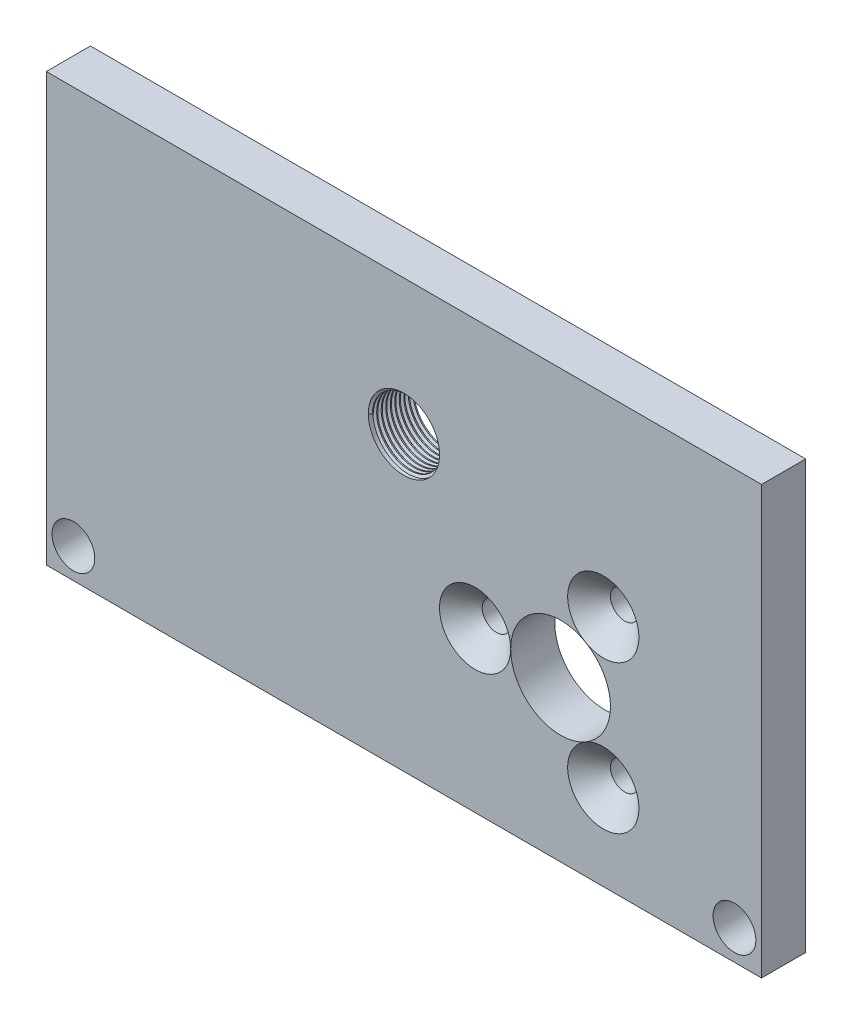
SolidWorks part; units mm, degrees
material "6063-T6"
ref_plane "Plano frontal" through (0, 0, 0) normal (0, 0, 1) x (1, 0, 0)
ref_plane "Plano superior" through (0, 0, 0) normal (0, 1, 0) x (1, 0, 0)
ref_plane "Plano direito" through (0, 0, 0) normal (1, 0, 0) x (0, 0, -1)
sketch "Esboço1" plane through (0, 0, 0) normal (0, 0, 1) x (1, 0, 0)
  line L0 (0, 5.5) -> (0, -19.5) construction
  line L1 (-25.1, 15) -> (25.1, 15)
  line L2 (-25.1, 15) -> (-25.1, -15)
  line L3 (-25.1, -15) -> (25.1, -15)
  line L4 (25.1, 15) -> (25.1, -15)
  line L5 (-25.1, 15) -> (25.1, -15) construction
  line L6 (-25.1, -15) -> (25.1, 15) construction
  line L7 (10.9941, -3.8) -> (10.9941, 4.1456) construction
  line L8 (10.9941, -3.8) -> (13.9941, 1.3962) construction
  circle A0 centre (0, 5.5) radius 2.5
  circle A1 centre (10.9941, -3.8) radius 11 construction
  circle A2 centre (10.9941, -3.8) radius 2.4 construction
  circle A3 centre (0, 5.5) radius 12 construction
  circle A4 centre (0, 5.5) radius 25 construction
  circle A5 centre (10.9941, -3.8) radius 3.5
  circle A6 centre (-23.2, -12.9) radius 1.5
  circle A7 centre (23.2, -12.9) radius 1.5
  circle A8 centre (13.9941, 1.3962) radius 1
  circle A9 centre (13.9941, -8.9962) radius 1
  circle A10 centre (4.9941, -3.8) radius 1
  point P0 (0, 0)
  point P12 (0, -19.5)
  point P30 (10.9941, -3.8)
  dimension "D3" = 5
  dimension "D4" = 22
  dimension "D5" = 0.2
  dimension "D6" = 4.8
  dimension "D7" = 24
  dimension "D8" = 50
  dimension "D10" = 7
  dimension "D11" = 3
  dimension "D14" = 2
  dimension "D1" = 50.2
  dimension "D2" = 30
  dimension "D9" = 4.5
  dimension "D12" = 2.1
  dimension "D13" = 1.9
  dimension "D15" = 30
  dimension "D16" = 6
  dimension "D17" = 3
extrude "Ressalto-extrusão1" add sketch "Esboço1" along normal blind 3.1
chamfer "Chanfro1" distance 1.5 angle 45 3 edges at (14.9941, -8.9962, 3.1) (14.9941, 1.3962, 3.1) (5.9941, -3.8, 3.1)
thread "Rosca2" pitch 0.3175 method extrude profile "Perfil da rosca2" start angle 0, offset 0, length 3, pitch 0.3175, diameter 5
ref_plane "Plano2" through (-2.5, 5.5, 3.1) normal (0, -1, 0) x (-1, 0, 0)
sketch "Perfil da rosca2" plane through (-2.5, 5.5, 3.1) normal (0, -1, 0) x (-1, 0, 0)
  line L0 (0, 0) -> (0, 0.3175) construction
  line L11 (0, 0) -> (0, 0.2778)
  line L12 (0, 0.2778) -> (-0.1719, 0.1786)
  line L13 (-0.1719, 0.1786) -> (-0.1719, 0.0992)
  line L15 (-0.1719, 0.0992) -> (0, 0)
  line L17 (-0.1719, 0.1389) -> (0, 0.1389) construction
  point P2 (0, 0)
  dimension "Pitch" = 0.3175
  dimension "Profile_Angle" = 60
  dimension "Profile_Land" = 0.0794
  dimension "Profile_Height" = 0.1719
